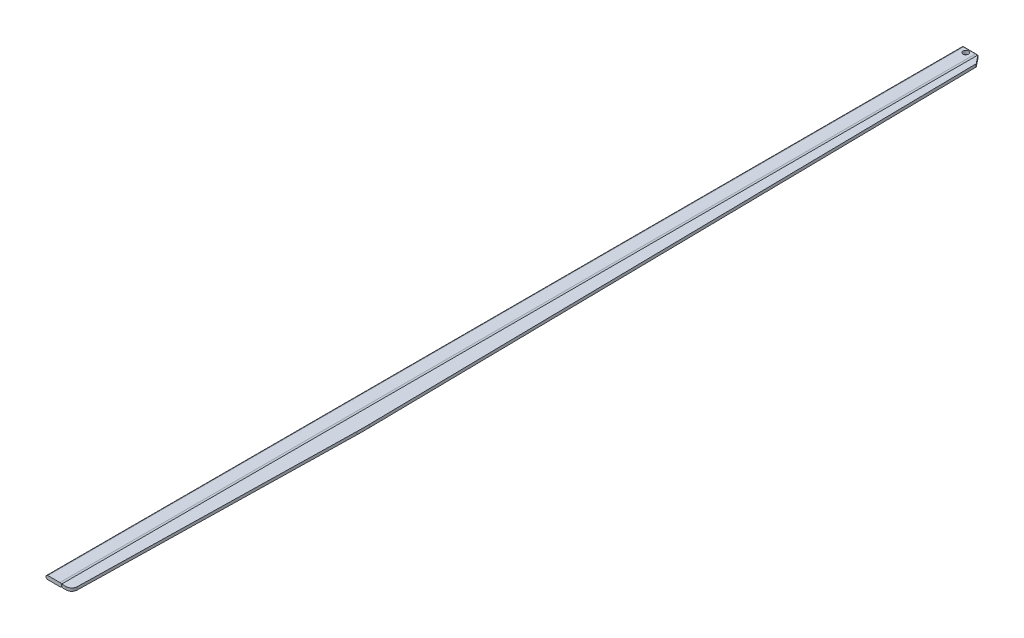
SolidWorks part; units mm, degrees
ref_plane "Front Plane" through (0, 0, 0) normal (0, 0, 1) x (1, 0, 0)
ref_plane "Top Plane" through (0, 0, 0) normal (0, 1, 0) x (1, 0, 0)
ref_plane "Right Plane" through (0, 0, 0) normal (1, 0, 0) x (0, 0, -1)
sketch "Sketch1" plane through (0, 0, 0) normal (0, 0, 1) x (1, 0, 0)
  line L0 (-165, 0) -> (165, 0) construction
  line L1 (-165, 50) -> (165, 50)
  line L2 (-165, -50) -> (165, -50)
  arc A0 (-165, 50) -> (-165, -50) centre (-165, 0) ccw
  arc A1 (165, -50) -> (165, 50) centre (165, 0) ccw
  point P3 (0, 0)
  point P8 (-215, 0)
  point P9 (215, 0)
  dimension "D2" = 100
  dimension "D1" = 430
sketch "Sketch2" plane through (0, 0, 0) normal (0, 1, 0) x (1, 0, 0)
  line L0 (0, 0) -> (0, -25000)
  dimension "D1" = 25000
sweep "Sweep1" add profiles "Sketch1" path "Sketch2"
sketch "Sketch3" plane through (0, 0, 0) normal (0, 1, 0) x (1, 0, 0)
  line L0 (215, 0) -> (395.7156, -230.4036)
  line L1 (395.7156, -230.4036) -> (638.1421, -17026.1865)
  line L2 (637.2415, -17367.5858) -> (489.6717, -24854.0692)
  line L3 (338.3547, -25001.107) -> (215, -25000)
  line L5 (215, 0) -> (215, -25000)
  arc A0 (638.1421, -17026.1865) -> (637.2415, -17367.5858) centre (-9360.8164, -17170.5091) cw
  arc A1 (489.6717, -24854.0692) -> (338.3547, -25001.107) centre (339.7008, -24851.1131) cw
  point P3 (638.7464, -17367.5858)
  point P8 (0, 0)
  point P9 (395.7156, -230.4036)
  point P10 (0, 0)
  point P15 (0, 0)
  dimension "D1" = 10000
  dimension "D2" = 150
sketch "Sketch4" plane through (0, 50, 0) normal (0, 1, 0) x (1, 0, 0)
  line L0 (0, 0) -> (0, -120) construction
  line L1 (165, 0) -> (-165, 0) construction
  circle A0 centre (0, -120) radius 75
  dimension "D1" = 150
  dimension "D2" = 120
extrude "Cut-Extrude1" cut sketch "Sketch4" against normal through all
fillet "Fillet1" radius 20 4 edges at (0, 50, 0) (215, 0, 0) (0, -50, 0) (-215, 0, 0)
extrude "Boss-Extrude1" add sketch "Sketch3" along normal blind 40 and the other way blind 40 separate body
